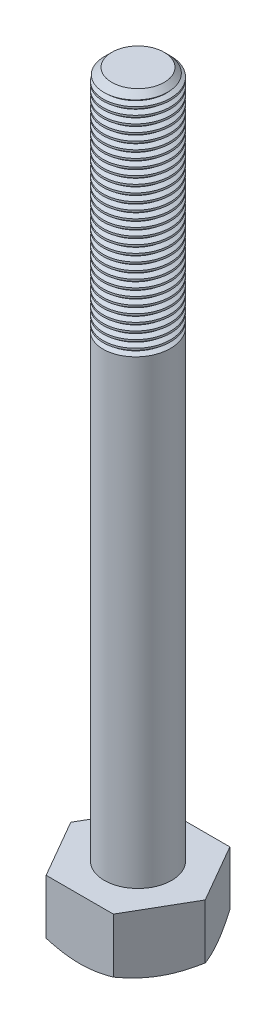
SolidWorks part; units mm, degrees
ref_plane "Front Plane" through (0, 0, 0) normal (0, 0, 1) x (1, 0, 0)
ref_plane "Top Plane" through (0, 0, 0) normal (0, 1, 0) x (1, 0, 0)
ref_plane "Right Plane" through (0, 0, 0) normal (1, 0, 0) x (0, 0, -1)
sketch "Sketch1" plane through (0, 0, 0) normal (0, 1, 0) x (1, 0, 0)
  line L1 (4.5, -7.7942) -> (9, 0)
  line L2 (9, 0) -> (4.5, 7.7942)
  line L3 (4.5, 7.7942) -> (-4.5, 7.7942)
  line L4 (-4.5, 7.7942) -> (-9, 0)
  line L5 (-9, 0) -> (-4.5, -7.7942)
  line L6 (-4.5, -7.7942) -> (4.5, -7.7942)
  circle A0 centre (0, 0) radius 4.5
  circle A1 centre (0, 0) radius 7.7942 construction
  dimension "D2" = 9
  dimension "D1" = 18
extrude "Boss-Extrude1" add sketch "Sketch1" along normal blind 8
extrude "Boss-Extrude2" add sketch "Sketch1<2>" along normal blind 100 contours A0 region at (0, 0, 0)
sketch "Sketch1<2>" plane through (0, 0, 0) normal (0, 1, 0) x (1, 0, 0) same geometry as "Sketch1"
sketch "Sketch2" plane through (0, 0, 0) normal (1, 0, 0) x (0, 0, -1)
  line L0 (0, 0) -> (0, -50000) construction
  line L1 (7.7942, 0) -> (10.588, 1.613)
  line L2 (10.588, 1.613) -> (10.588, 0)
  line L3 (10.588, 0) -> (7.7942, 0)
  dimension "D1" = 30
revolve "Cut-Revolve1" cut sketch "Sketch2" angle 360 about L0
chamfer "Chamfer1" distance 1 angle 45 1 edges at (0, 100, 4.5)
thread "Thread1" pitch 1 method cut profile "Thread Profile1" start angle 0, offset 1, length 30, pitch 1, diameter 9
ref_plane "Plane1" through (-4.5, 100, 0) normal (0, 0, -1) x (1, 0, 0)
sketch "Thread Profile1" plane through (-4.5, 100, 0) normal (0, 0, -1) x (1, 0, 0)
  line L0 (0, 0) -> (0, 1) construction
  line L1 (0, 0) -> (0.5413, 0.3125)
  line L2 (0.5413, 0.3125) -> (0.5413, 0.4375)
  line L3 (0.5413, 0.4375) -> (0, 0.75)
  line L4 (0.5413, 0.375) -> (0, 0.375) construction
  line L11 (0, 0) -> (0, 0.75)
  point P2 (0, 0)
  dimension "Pitch" = 1
  dimension "Profile_Angle" = 60
  dimension "Profile_Land" = 0.125
  dimension "Profile_Height" = 0.5413
